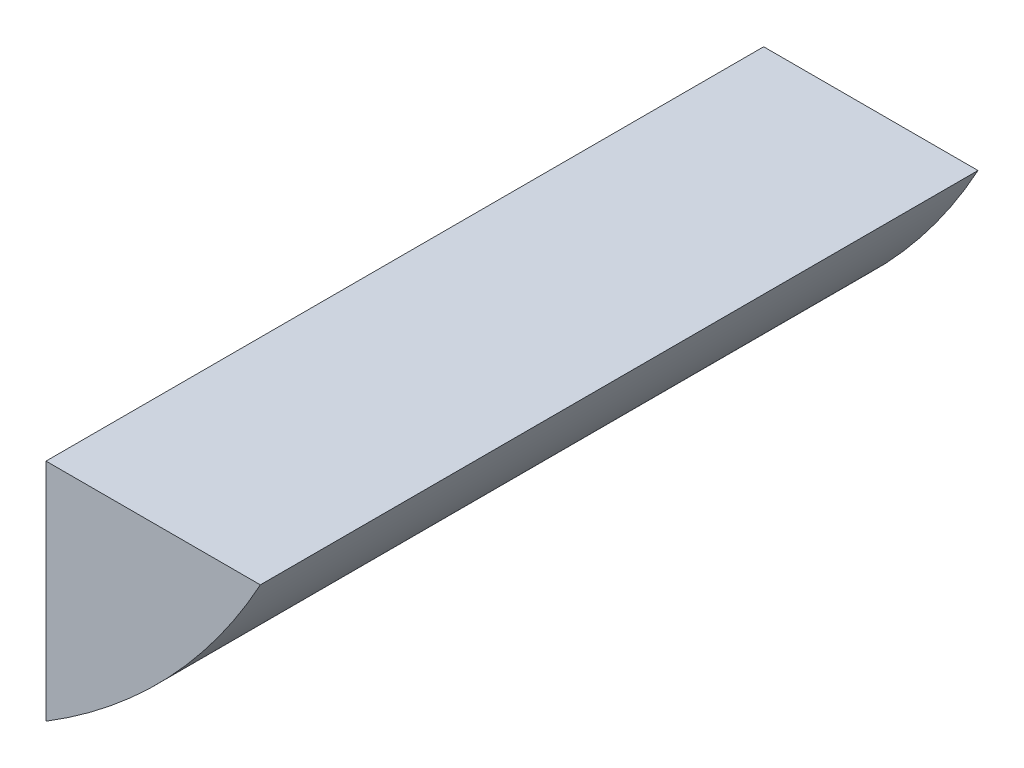
SolidWorks part; units mm, degrees
material "ABS"
ref_plane "Płaszczyzna przednia" through (0, 0, 0) normal (0, 0, 1) x (1, 0, 0)
ref_plane "Płaszczyzna górna" through (0, 0, 0) normal (0, 1, 0) x (1, 0, 0)
ref_plane "Płaszczyzna prawa" through (0, 0, 0) normal (1, 0, 0) x (0, 0, -1)
sketch "Szkic1" plane through (0, 0, 0) normal (0, 0, 1) x (1, 0, 0)
  line L7 (15.9573, -36.0859) -> (18.0264, -34.8795)
  line L13 (18.0264, -54.1634) -> (18.0264, -20.1634) construction
  line L14 (32.9596, -19.1815) -> (18.0264, -19.1815)
  line L15 (18.0264, -19.1815) -> (18.0264, -34.8795)
  arc A7 (18.0264, -34.8795) -> (32.9596, -19.1815) centre (-3.9829, 1.0093) ccw
  point P0 (19.0954, -25.0519)
extrude "Dodanie-wyciągnięcie1" add sketch "Szkic1" along normal blind 50 contours L7 A7 L14 L15 region at (23.4367, -24.8627, 0)
